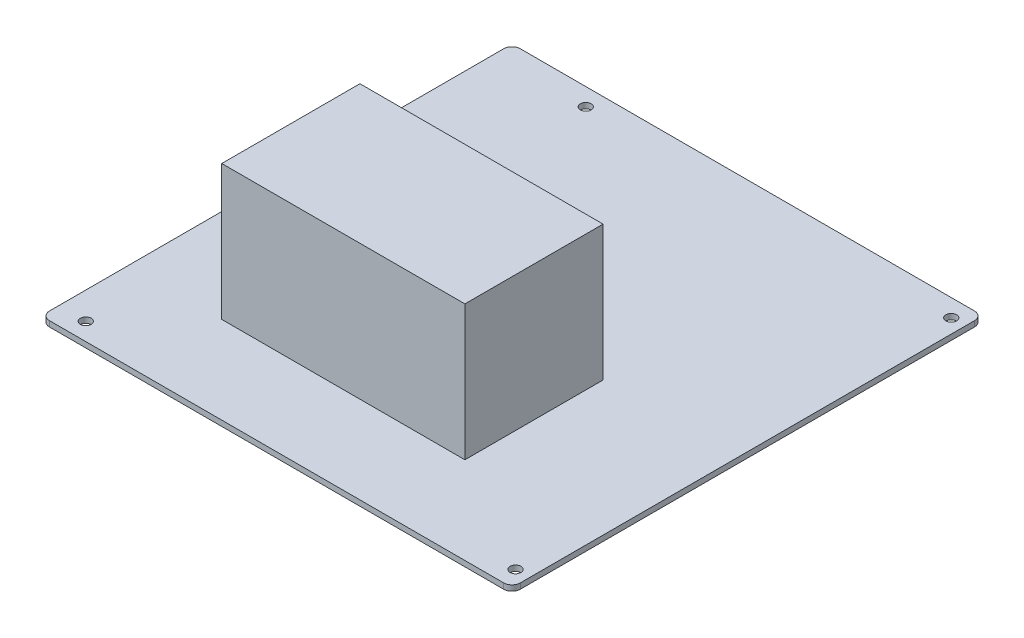
SolidWorks part; units mm, degrees
ref_plane "Front" through (0, 0, 0) normal (0, 0, 1) x (1, 0, 0)
ref_plane "Top" through (0, 0, 0) normal (0, 1, 0) x (1, 0, 0)
ref_plane "Right" through (0, 0, 0) normal (1, 0, 0) x (0, 0, -1)
sketch "Sketch1" plane through (0, 0, 0) normal (0, 1, 0) x (1, 0, 0)
  line L1 (85.09, 85.09) -> (-85.09, 85.09)
  line L2 (85.09, 85.09) -> (85.09, -85.09)
  line L3 (85.09, -85.09) -> (-85.09, -85.09)
  line L4 (-85.09, 85.09) -> (-85.09, -85.09)
  line L5 (85.09, 85.09) -> (-85.09, -85.09) construction
  line L6 (85.09, -85.09) -> (-85.09, 85.09) construction
  point P0 (0, 0)
  dimension "D1" = 170.18
  dimension "D2" = 170.18
extrude "Boss-Extrude1" add sketch "Sketch1" along normal blind 2
sketch "Sketch2" plane through (0, 2, 0) normal (0, 1, 0) x (1, 0, 0)
  line L1 (-51.3234, -3.6387) -> (36.5538, -3.6387)
  line L2 (-51.3234, -3.6387) -> (-51.3234, -53.5762)
  line L3 (-51.3234, -53.5762) -> (36.5538, -53.5762)
  line L4 (36.5538, -3.6387) -> (36.5538, -53.5762)
  line L5 (-51.3234, -3.6387) -> (36.5538, -53.5762) construction
  line L6 (-51.3234, -53.5762) -> (36.5538, -3.6387) construction
  point P0 (-7.3848, -28.6074)
extrude "Boss-Extrude2" add sketch "Sketch2" along normal blind 48.8
fillet "Fillet1" radius 3 4 edges at (-85.09, 1, -85.09) (85.09, 1, -85.09) (85.09, 1, 85.09) (-85.09, 1, 85.09)
hole_wizard "Ø3.9 (3.9) Diameter Hole1" positions "Sketch3" profile "Sketch4" hole size "Ø3.9" standard "ANSI Metric"
sketch "Sketch3" plane through (0, 2, 0) normal (0, 1, 0) x (1, 0, 0)
  line L0 (-82.09, -85.09) -> (82.09, -85.09) construction
  line L1 (85.09, -82.09) -> (85.09, 82.09) construction
  line L3 (-52.07, 78.74) -> (80.01, 78.74) construction
  point P0 (-75.29, -78.74)
  point P2 (80.01, -78.74)
  point P4 (80.01, 78.74)
  point P6 (-52.07, 78.74)
  dimension "D1" = 6.35
  dimension "D2" = 6.35
  dimension "D3" = 5.08
  dimension "D4" = 5.08
  dimension "D5" = 157.48
  dimension "D6" = 132.08
  dimension "D7" = 155.3
sketch "Sketch4" plane through (-75.29, 2, 78.74) normal (1, 0, 0) x (0, 0, 1)
  line L0 (0, 0) -> (0, 19.9217)
  line L1 (0, 19.9217) -> (1.95, 18.75)
  line L2 (1.95, 18.75) -> (1.95, 0)
  line L5 (1.95, 0) -> (0, 0)
  line L10 (0, 19.9217) -> (-1.95, 18.75) construction
  line L11 (0, -6.35) -> (0, 107.95) construction
  dimension "Hole Dia." = 3.9
  dimension "Hole Depth" = 18.75
  dimension "Drill Angle" = 118
sketch "Sketch5" plane through (0, 2, 0) normal (0, 1, 0) x (1, 0, 0)
  line L1 (55.5339, -83.6636) -> (59.9742, -83.6636)
  line L2 (55.5339, -83.6636) -> (55.5339, -75.8548)
  line L3 (55.5339, -75.8548) -> (59.9742, -75.8548)
  line L4 (59.9742, -83.6636) -> (59.9742, -75.8548)
  line L5 (55.5339, -83.6636) -> (59.9742, -75.8548) construction
  line L6 (55.5339, -75.8548) -> (59.9742, -83.6636) construction
  point P0 (57.754, -79.7592)
extrude "Boss-Extrude3" [suppressed] add sketch "Sketch5" along normal blind 50
